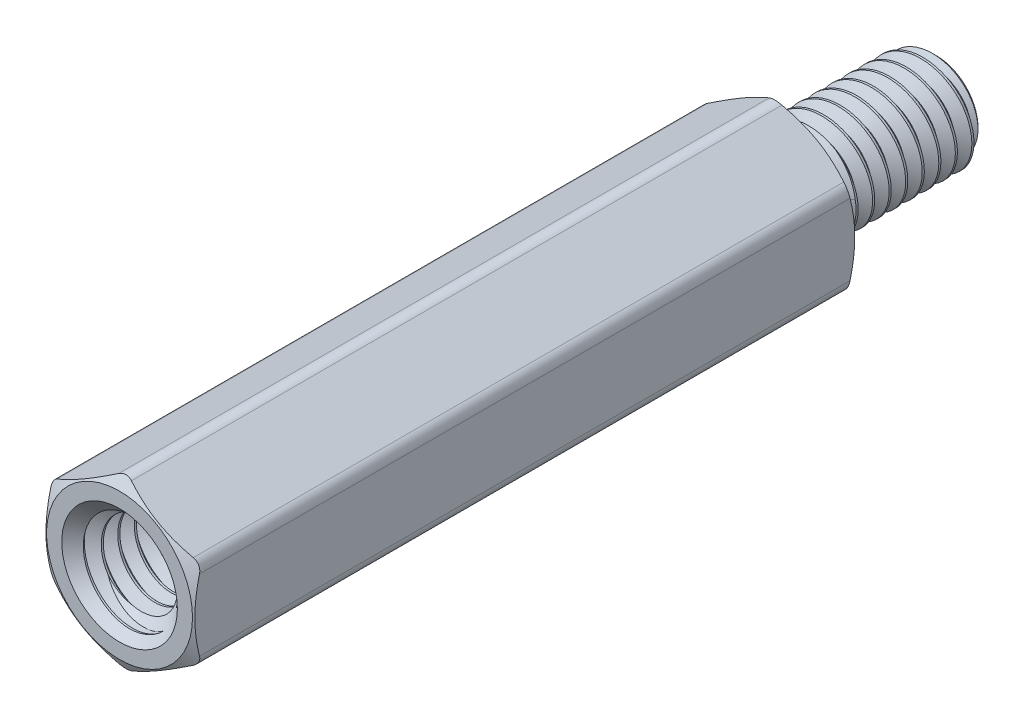
SolidWorks part; units mm, degrees
material "AISI 304"
ref_plane "Front Plane" through (0, 0, 0) normal (0, 0, 1) x (1, 0, 0)
ref_plane "Top Plane" through (0, 0, 0) normal (0, 1, 0) x (1, 0, 0)
ref_plane "Right Plane" through (0, 0, 0) normal (1, 0, 0) x (0, 0, -1)
sketch "Sketch1" plane through (0, 0, 0) normal (0, 0, 1) x (1, 0, 0)
  line L1 (2.25, 1.299) -> (0, 2.5981)
  line L2 (0, 2.5981) -> (-2.25, 1.299)
  line L3 (-2.25, 1.299) -> (-2.25, -1.299)
  line L4 (-2.25, -1.299) -> (0, -2.5981)
  line L5 (0, -2.5981) -> (2.25, -1.299)
  line L6 (2.25, -1.299) -> (2.25, 1.299)
  circle A0 centre (0, 0) radius 2.25 construction
  point P10 (0, -2.25)
  dimension "Hex Size" = 4.5
sketch "Sketch2" plane through (0, 0, 0) normal (1, 0, 0) x (0, 0, -1)
  line L0 (4.7, 0) -> (-20, 0) construction
  line L2 (0, 1.5) -> (0, -1.5) construction
  line L3 (-13.6, 1.5) -> (-13.6, -1.5) construction
  line L4 (-20.4688, 1.5541) -> (-20.2187, 1.1211) construction
  line L5 (-20.2187, 1.1211) -> (-19.9688, 1.5541) construction
  line L6 (-19.9688, 1.5541) -> (-20.4688, 1.5541) construction
  line L7 (-20.4375, 1.5) -> (-20, 1.5) construction
  line L8 (-20.25, 1.1752) -> (-20.1875, 1.1752) construction
  line L9 (-20.2188, 1.1752) -> (-20.2187, 1.1211) construction
  line L10 (-20.2188, 1.5) -> (-20.2188, 1.5541) construction
  line L11 (4.6688, 1.5541) -> (5.1688, 1.5541) construction
  line L12 (5.1688, 1.5541) -> (4.9188, 1.1211) construction
  line L13 (4.9188, 1.1211) -> (4.6688, 1.5541) construction
  line L14 (4.7, 1.5) -> (5.1375, 1.5) construction
  line L15 (4.8875, 1.1752) -> (4.95, 1.1752) construction
  line L16 (4.9188, 1.1752) -> (4.9188, 1.1211) construction
  line L17 (4.9188, 1.5) -> (4.9188, 1.5541) construction
  line L18 (0, 2.5981) -> (-20, 2.5981) construction
  point P6 (0, 0)
  point P9 (-13.6, 0)
  dimension "Length" = 20
sketch "Sketch3" plane through (0, 0, 0) normal (1, 0, 0) x (0, 0, -1)
  line L0 (-13.6, 0) -> (4.7, 0)
  line L1 (-13.6, 1.5) -> (-13.6, -1.5) construction
  line L2 (4.7, 0) -> (4.7, 1.25)
  line L3 (4.7, 1.25) -> (4.45, 1.5)
  line L4 (4.45, 1.5) -> (0.7515, 1.5)
  line L5 (0.7515, 1.5) -> (0.564, 1.1752)
  line L6 (-13.6, 0) -> (-13.6, 1.25)
  line L7 (-13.6, 1.25) -> (-13.85, 1.5)
  line L8 (-13.85, 1.5) -> (-19.75, 1.5)
  line L9 (-19.75, 1.5) -> (-20, 1.75)
  line L10 (4.45, 0) -> (4.45, -1.5) construction
  line L11 (-20, 1.75) -> (-20, 2.25)
  line L12 (-20, 2.25) -> (0, 2.25)
  line L14 (0.564, 1.1752) -> (0.25, 1.1752)
  line L15 (0, 1.4252) -> (0, 2.25)
  arc A0 (0, 1.4252) -> (0.25, 1.1752) centre (0.25, 1.4252) ccw
  point P5 (-20, -2.25)
  point P8 (-18.75, -1.5)
  point P9 (3.45, -1.5)
  point P27 (0, 1.1752)
  dimension "D4" = 0.25
  dimension "D2" = 0.25
  dimension "D1" = 45
  dimension "D6" = 1.25
  dimension "D7" = 60
  dimension "D3" = 1.25
  dimension "D5" = 0.564
revolve "Revolve1" add sketch "Sketch3" angle 360 about L0 region at (0, 1.1462, 6.4467)
sketch "Sketch4" plane through (0, 0, 20) normal (0, 0, 1) x (1, 0, 0)
  line L0 (0, 2.25) -> (0, 1.5) construction
  line L1 (-2.25, 1.299) -> (-2.25, -1.299)
  line L2 (-2.25, -1.299) -> (0, -2.5981)
  line L3 (0, -2.5981) -> (2.25, -1.299)
  line L4 (2.25, -1.299) -> (2.25, 1.299)
  line L5 (2.25, 1.299) -> (0, 2.5981)
  line L6 (0, 2.5981) -> (-2.25, 1.299)
  circle A0 centre (0, 0) radius 2.25 construction
  circle A1 centre (0, 0) radius 1.875
  circle A2 centre (0, 0) radius 2.25 construction
  point P16 (0, 1.875)
extrude "Boss-Extrude1" add sketch "Sketch4" against normal up to surface (20 mm away) up to face at (0, 2.25, 0)
sketch "Sketch5" plane through (0, 0, 20) normal (0, 0, 1) x (1, 0, 0)
  line L0 (-0.8604, 1.2287) -> (0.8604, -1.2287) construction
  line L1 (0, 1.5) -> (0, -1.5) construction
  line L3 (0, -2.7928) -> (0, 2.7928) construction
  circle A0 centre (0, 0) radius 2.205
  point P11 (0.8604, -1.2287)
  dimension "D1" = 4.41
  dimension "D2" = 35
extrude "Cut-Extrude1" cut sketch "Sketch5" against normal through all draft 60 flip side to cut
sketch "Sketch6" plane through (0, 0, 0) normal (0, 0, -1) x (-1, 0, 0)
  circle A0 centre (0, 0) radius 2.205
  circle A1 centre (0, 0) radius 2.205 construction
extrude "Cut-Extrude2" cut sketch "Sketch6" against normal through all draft 60 flip side to cut
fillet "Fillet1" radius 0.3825 6 edges at (0, 2.5981, 10) (-2.25, -1.299, 10) (0, -2.5981, 10) (2.25, -1.299, 10) (2.25, 1.299, 10) (-2.25, 1.299, 10)
sketch "Drawing1" plane through (0, 0, 0) normal (1, 0, 0) x (0, 0, -1)
  line L0 (-20, 1.5) -> (-13.6, 1.5) construction
  line L1 (-13.6, 1.5) -> (-13.6, -1.5) construction
  line L2 (-13.6, -1.5) -> (-20, -1.5) construction
sketch "Sketch7" plane through (0, 0, 0) normal (-1, 0, 0) x (0, 0, 1)
  line L0 (-4.8875, 1.1752) -> (-4.95, 1.1752)
  line L1 (-4.95, 1.1752) -> (-5.1531, 1.5271)
  line L2 (-5.1688, 1.5541) -> (-4.9188, 1.1211) construction
  line L3 (-5.1531, 1.5271) -> (-4.6844, 1.5271)
  line L4 (-4.9188, 1.1211) -> (-4.6688, 1.5541) construction
  line L5 (-4.6844, 1.5271) -> (-4.8875, 1.1752)
  line L6 (-4.9188, 1.5) -> (-4.9188, 1.5541) construction
  point P12 (-4.9188, 1.5271)
sketch "Sketch8" plane through (0, 0, -4.7) normal (0, 0, -1) x (-1, 0, 0)
  circle A0 centre (0, 0) radius 1.5
curve "Helix/Spiral1" pitch 0.5 height 4.559 radius 1.5 centre (0, 0, -4.7) axis (0, 0, 1) start towards (0, 1, 0)
sweep "Cut-Sweep1" cut profiles "Sketch7" path "Helix/Spiral1" align with end faces yes
sketch "Sketch9" plane through (0, 0, 13.6) normal (0, 0, 1) x (1, 0, 0)
  circle A0 centre (0, 0) radius 1.75
extrude "Boss-Extrude2" add sketch "Sketch9" along normal up to surface (6.4 mm away) up to face at (0, 1.75, 20)
sketch "Sketch10" plane through (0, 0, 0) normal (1, 0, 0) x (0, 0, -1)
  line L0 (4.7, 0) -> (-20, 0) construction
  line L1 (-13.6, 1.5) -> (-20, 1.5)
  line L2 (-13.6, 1.5) -> (-13.6, 0)
  line L3 (-13.6, 0) -> (-20, 0)
  line L4 (-20, 1.5) -> (-20, 0)
revolve "Revolve2" add sketch "Sketch10" angle 360 about L0
sketch "Sketch11" plane through (0, 0, 20) normal (0, 0, 1) x (1, 0, 0)
  circle A0 centre (0, 0) radius 1.5
  circle A1 centre (0, 0) radius 1.5 construction
sketch "Sketch12" plane through (0, 0, 0) normal (1, 0, 0) x (0, 0, -1)
  line L0 (-20.25, 1.1752) -> (-20.1875, 1.1752)
  line L1 (-20.1875, 1.1752) -> (-19.9844, 1.5271)
  line L2 (-20.2187, 1.1211) -> (-19.9688, 1.5541) construction
  line L3 (-19.9844, 1.5271) -> (-20.4531, 1.5271)
  line L4 (-20.4688, 1.5541) -> (-20.2187, 1.1211) construction
  line L5 (-20.4531, 1.5271) -> (-20.25, 1.1752)
  line L6 (-20.2188, 1.5) -> (-20.2188, 1.5541) construction
  point P12 (-20.2188, 1.5271)
curve "Helix/Spiral2" pitch 0.5 height 6.9 radius 1.5 centre (0, 0, 20) axis (0, 0, -1) start towards (0, 1, 0)
sweep "Cut-Sweep2" cut profiles "Sketch12" path "Helix/Spiral2" align with end faces yes
combine bodies "Combine1" operation type subtract main body 113 bodies to subtract 114
sketch "Sketch13" plane through (0, 0, 20) normal (0, 0, 1) x (1, 0, 0)
  circle A0 centre (0, 0) radius 1.7475
  dimension "D1" = 3.495
extrude "Cut-Extrude3" cut sketch "Sketch13" against normal through all draft 45
equation "\"Thread Pitch (B)/8@Sketch2\" = \"Thread Pitch (B)@Sketch2\" / 8"
equation "\"Thread Pitch (A)/8@Sketch2\" = \"Thread Pitch (A)@Sketch2\" / 8"
equation "\"D1@Sketch5\"=\"Hex Size@Sketch1\" * .98"
equation "\"D1@Fillet1\"=\"Hex Size@Sketch1\" * .085"
equation "\"D2@Sketch3\"=\"Thread Pitch (A)@Sketch2\" * .5"
equation "\"D4@Sketch3\" = \"D2@Sketch3\""
equation "\"D6@Sketch3\" = \"Thread Pitch (A)@Sketch2\" * 2.5"
equation "\"D3@Helix/Spiral1\" = \"Thread Length (A)@Sketch2\" - \"D5@Sketch3\" * .25"
equation "\"D4@Helix/Spiral1\" = \"Thread Pitch (A)@Sketch2\""
equation "\"D3@Sketch3\" = \"Thread Pitch (B)@Sketch2\" * 2.5"
equation "\"D5@Sketch3\" = \"Thread Length (A)@Sketch2\" * .12"
equation "\"D3@Helix/Spiral2\" = \"Minimum Thread Length (B)@Sketch2\" + \"Thread Pitch (B)@Sketch2\""
equation "\"D4@Helix/Spiral2\" = \"Thread Pitch (B)@Sketch2\""
equation "\"D1@Sketch13\"=(\"Hex Size@Sketch1\"-\"Thread Size (A)@Sketch2\")*.33+\"Thread Size (A)@Sketch2\""
